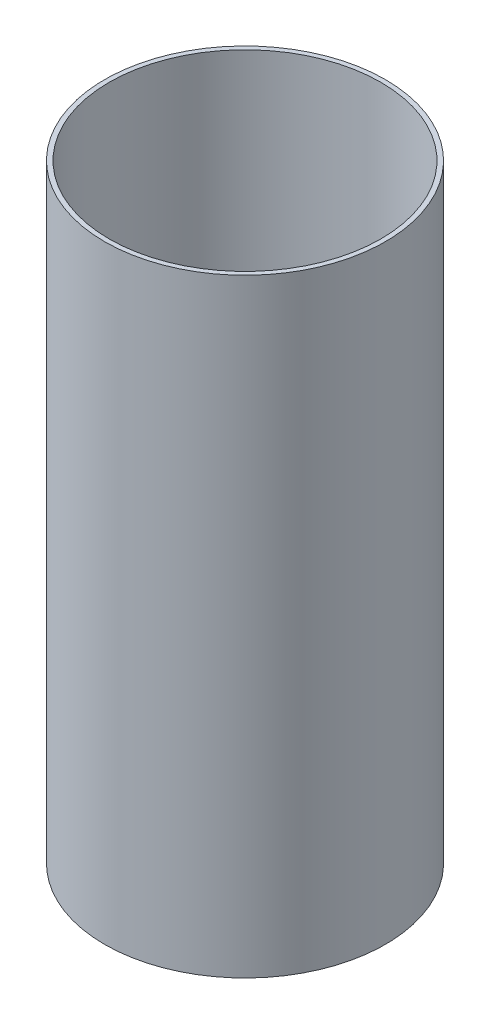
SolidWorks part; units mm, degrees
material "A-Glass Fiber"
ref_plane "Front Plane" through (0, 0, 0) normal (0, 0, 1) x (1, 0, 0)
ref_plane "Top Plane" through (0, 0, 0) normal (0, 1, 0) x (1, 0, 0)
ref_plane "Right Plane" through (0, 0, 0) normal (1, 0, 0) x (0, 0, -1)
sketch "Sketch1" plane through (0, 0, 0) normal (0, 1, 0) x (1, 0, 0)
  circle A0 centre (0, 0) radius 76.1746
  circle A1 centre (0, 0) radius 73.66
  dimension "D1" = 152.3492
  dimension "D2" = 147.32
extrude "Boss-Extrude1" add sketch "Sketch1" along normal blind 330.2
equation "\"Mid_Coupler_Length\"= 13in"
equation "\"D1@Boss-Extrude1\"=\"Mid_Coupler_Length\""
